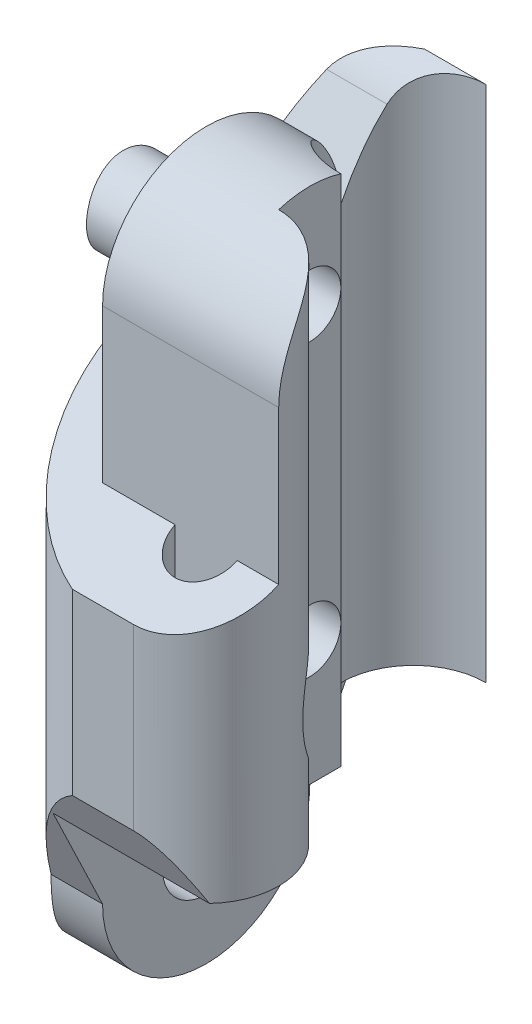
SolidWorks part; units mm, degrees
ref_plane "Front Plane" through (0, 0, 0) normal (0, 0, 1) x (1, 0, 0)
ref_plane "Top Plane" through (0, 0, 0) normal (0, 1, 0) x (1, 0, 0)
ref_plane "Right Plane" through (0, 0, 0) normal (1, 0, 0) x (0, 0, -1)
sketch "Sketch1" plane through (0, 0, 0) normal (0, 1, 0) x (1, 0, 0)
  line L0 (-2.958, 8.5) -> (2.958, 8.5)
  line L1 (-2.958, -8.5) -> (2.958, -8.5)
  arc A0 (-2.958, 8.5) -> (-2.958, -8.5) centre (0, 0) ccw
  arc A1 (2.958, 8.5) -> (2.958, -8.5) centre (0, 0) cw
  point P9 (-9, 0)
  point P10 (9, 0)
  dimension "D1" = 18
  dimension "D2" = 17
extrude "Boss-Extrude1" add sketch "Sketch1" along normal blind 35
sketch "Sketch2" plane through (0, 0, 0) normal (0, -1, 0) x (1, 0, 0)
  line L0 (1.5, 5) -> (-1.5, 5)
  line L1 (1.5, -5) -> (-1.5, -5)
  line L2 (0, 5) -> (0, -5) construction
  arc A2 (-1.5, 5) -> (1.5, 5) centre (0, 5) cw
  arc A3 (-1.5, -5) -> (1.5, -5) centre (0, -5) ccw
  dimension "D1" = 10
  dimension "D2" = 1.5
extrude "Cut-Extrude1" cut sketch "Sketch2" against normal blind 35
sketch "Sketch3" plane through (0, 0, -8.5) normal (0, 0, -1) x (-1, 0, 0)
  line L0 (5, 0) -> (5, 10)
  line L1 (5, 10) -> (-5, 10)
  line L2 (-5, 10) -> (-5, 0)
  line L3 (5, 0) -> (-5, 0)
  line L4 (-2.958, 0) -> (2.958, 0) construction
  point P10 (0, 0)
  dimension "D1" = 10
  dimension "D2" = 10
extrude "Cut-Extrude2" cut sketch "Sketch3" against normal up to surface (17 mm away) up to face at (0, 17.5, 8.5)
sketch "Sketch4" plane through (5, 0, 0) normal (-1, 0, 0) x (0, 0, 1)
  line L0 (-7.4833, 10) -> (-5, 5)
  line L1 (8.5, 12.3086) -> (5, 5)
  line L2 (7.4833, 0) -> (-7.4833, 0) construction
  line L3 (-7.4833, 10) -> (-9.8579, -1.8222)
  line L4 (-9.8579, -1.8222) -> (9.8579, -1.8222)
  line L6 (8.5, 35) -> (8.5, 10) construction
  line L7 (9.8579, -1.8222) -> (8.5, 12.3086)
  arc A0 (-5, 5) -> (5, 5) centre (0, 5) ccw
  circle A1 centre (0, 5) radius 2.1
  point P7 (0, 0)
  dimension "D1" = 4.2
  dimension "D2" = 5
  dimension "D3" = 12.0584
  dimension "D4" = 37.769
extrude "Cut-Extrude3" cut sketch "Sketch4" against normal mid plane 35
ref_plane "Plane1" through (-2.958, 0, 0) normal (-1, 0, 0) x (0, 0, 1)
sketch "Sketch6" plane through (-2.958, 0, 0) normal (-1, 0, 0) x (0, 0, 1)
  line L0 (8.5, 20.9294) -> (0, 25)
  line L1 (8.5, 35) -> (8.5, 12.3086) construction
  line L2 (-5, 30) -> (-6.7559, 33.5353)
  line L3 (8.5, 35) -> (-8.5, 35) construction
  line L4 (8.5, 20.9294) -> (17.803, 42.886)
  line L6 (-7.4833, 10) -> (-5, 5) construction
  line L7 (-8.5, 35) -> (17.803, 42.886)
  line L8 (5, 5) -> (8.5, 12.3086) construction
  arc A0 (0, 25) -> (-5, 30) centre (0, 30) cw
  circle A1 centre (0, 30) radius 2
  arc A2 (-6.7559, 33.5353) -> (-8.5, 35) centre (-9.3069, 32.2683) ccw
  dimension "D1" = 5
  dimension "D3" = 4
  dimension "D2" = 5
  dimension "D4" = 8.5
  dimension "D5" = 90
extrude "Cut-Extrude5" cut sketch "Sketch6" against normal blind 9.6 from surface starting at face at (5, 7.1, 0)
sketch "Sketch7" plane through (5, 0, 0) normal (1, 0, 0) x (0, 0, -1)
  line L0 (5, 30) -> (6.7559, 33.5353)
  line L2 (-8.3419, 47.5367) -> (-13.1682, 33.5285)
  line L3 (-7.4833, 35) -> (7.4833, 35) construction
  line L4 (-5, 30) -> (-5, 22.6055)
  line L5 (-7.4833, 21.4163) -> (0, 25) construction
  line L6 (-5, 22.6055) -> (-9.913, 20.2527)
  line L7 (-9.913, 20.2527) -> (-13.1682, 33.5285)
  line L8 (6.7559, 33.5353) -> (5, 30) construction
  line L9 (8.5, 35) -> (-8.3419, 47.5367)
  arc A0 (5, 30) -> (-5, 30) centre (0, 30) ccw
  arc A1 (6.7559, 33.5353) -> (8.5, 35) centre (9.3069, 32.2683) cw
  arc A2 (7.4833, 34.4564) -> (6.7559, 33.5353) centre (9.3069, 32.2683) ccw construction
  dimension "D1" = 5
fillet "Fillet3" radius 1 4 edges at (0, 10, -6.5) (0, 10, -5) (0, 10, 6.5) (0, 10, 5)
extrude "Cut-Extrude6" cut sketch "Sketch6<3>" along normal blind 6.604 from surface starting at face at (-5, 2.9, 0)
sketch "Sketch6<3>" plane through (-2.958, 0, 0) normal (-1, 0, 0) x (0, 0, 1) same geometry as "Sketch6"
extrude "Cut-Extrude7" cut sketch "Sketch7" against normal blind 14.986
sketch "Sketch8" plane through (0, 10, 0) normal (0, -1, 0) x (1, 0, 0)
  line L0 (0, 1.5) -> (0, -1.5)
  line L1 (-2.958, -8.5) -> (2.958, -8.5) construction
  line L2 (2.958, 8.5) -> (-2.958, 8.5) construction
  line L3 (0, 8.5) -> (-4.7901, 15.219)
  line L4 (-4.7901, 15.219) -> (34.9648, -1.5)
  line L5 (34.9648, -1.5) -> (-4.7901, -16.0136)
  line L6 (-4.7901, -16.0136) -> (0, -8.5)
  arc A0 (0, -1.5) -> (0, -8.5) centre (0, -5) ccw
  arc A1 (0, 1.5) -> (0, 8.5) centre (0, 5) ccw
  arc A4 (2.2913, 4) -> (0.7187, 7.3945) centre (0, 5) ccw construction
  arc A5 (-2.2913, -4) -> (2.2913, -4) centre (0, -5) ccw construction
extrude "Cut-Extrude8" cut sketch "Sketch8" against normal mid plane 62.992
sketch "Sketch9" plane through (0, 0, 0) normal (1, 0, 0) x (0, 0, -1)
  line L1 (1.5, 10) -> (-1.5, 10) construction
  circle A0 centre (0, 16) radius 1.5
  dimension "D2" = 3
  dimension "D1" = 6
extrude "Cut-Extrude9" cut sketch "Sketch9" against normal blind 14.224
sketch "Sketch13" plane through (0, 0, 0) normal (1, 0, 0) x (0, 0, -1)
  line L1 (1.5, 34.7697) -> (1.5, 16) construction
  circle A0 centre (0, 30) radius 1.5
  circle A2 centre (0, 30) radius 2 construction
sketch "Sketch14" plane through (0, 0, 0) normal (1, 0, 0) x (0, 0, -1)
  line L0 (0, 12.5) -> (0, 19.5)
  arc A0 (0, 19.5) -> (0, 12.5) centre (0, 16) ccw
  circle A1 centre (0, 16) radius 1.5 construction
  dimension "D1" = 3.5
extrude "Cut-Extrude11" cut sketch "Sketch14" along normal blind 6.048
extrude "Cut-Extrude12" cut sketch "Sketch13" against normal blind 3
sketch "Sketch15" plane through (0, 0, 0) normal (1, 0, 0) x (0, 0, -1)
  circle A0 centre (0, 16) radius 2.75
  dimension "D1" = 5.5
extrude "Cut-Extrude13" cut sketch "Sketch15" against normal blind 7.572 from offset 5.5 offset against normal yes
